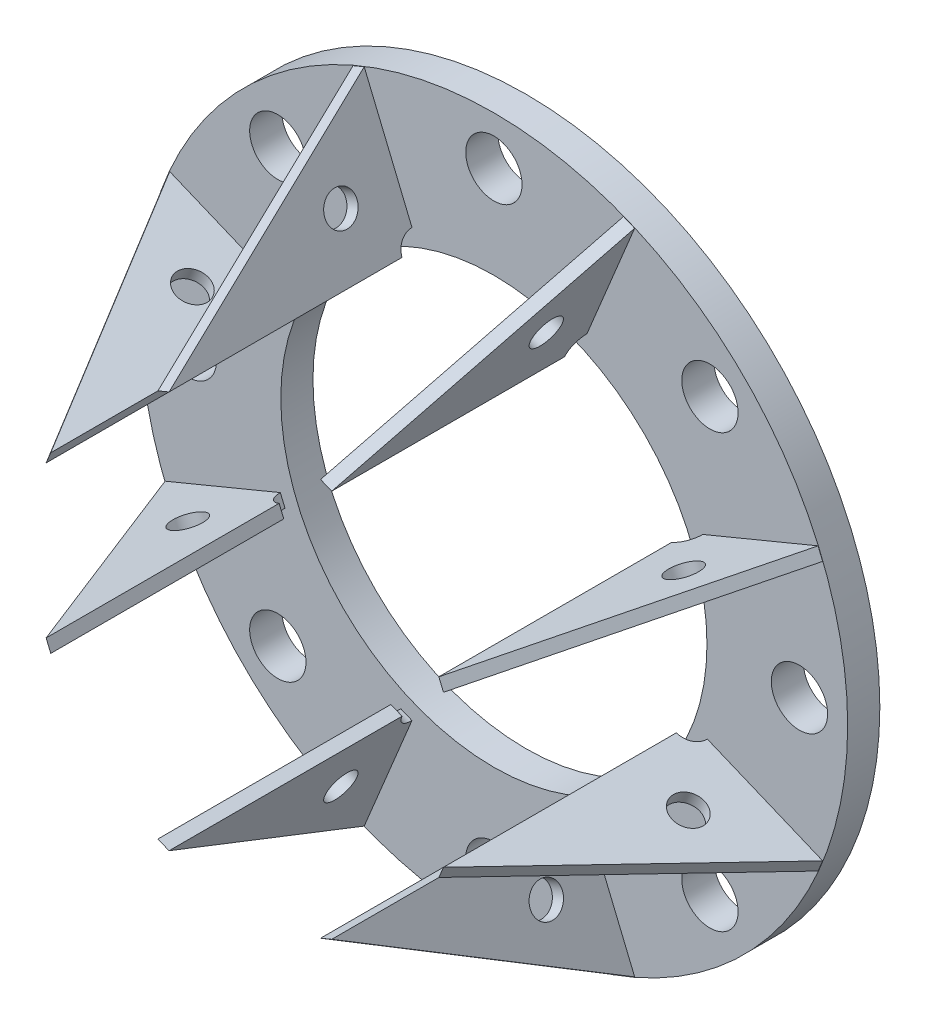
SolidWorks part; units mm, degrees
ref_plane "Front Plane" through (0, 0, 0) normal (0, 0, 1) x (1, 0, 0)
ref_plane "Top Plane" through (0, 0, 0) normal (0, 1, 0) x (1, 0, 0)
ref_plane "Right Plane" through (0, 0, 0) normal (1, 0, 0) x (0, 0, -1)
sketch "Sketch1" plane through (0, 0, 0) normal (0, 0, 1) x (1, 0, 0)
  circle A0 centre (0, 0) radius 84.1375
  circle A1 centre (0, 0) radius 139.7
  dimension "D1" = 168.275
  dimension "D2" = 279.4
extrude "Extrude1" add sketch "Sketch1" along normal blind 12.7
hole_wizard " (0.625) Diameter Hole1" positions "3DSketch1" profile "Sketch2" hole size "7/8" standard "Ansi Inch"
sketch3d "3DSketch1"
  line L10 (0, 139.7, 12.7) -> (0, 0, 12.7) construction
  circle A2 centre (0, 0, 12.7) radius 139.7 construction
  circle A3 centre (0, 0, 12.7) radius 139.7 construction
  point P5 (0, 120.65, 12.7)
  point P24 (0, 0, 152.4)
  point P26 (0, 0, 152.4)
  dimension "D1" = 120.65
sketch "Sketch2" plane through (0, 120.65, 12.7) normal (1, 0, 0) x (0, -1, 0)
  line L0 (0, 0) -> (0, 32.0771)
  line L1 (0, 32.0771) -> (11.1125, 25.4)
  line L2 (11.1125, 25.4) -> (11.1125, 0)
  line L5 (11.1125, 0) -> (0, 0)
  line L10 (0, 32.0771) -> (-11.1125, 25.4) construction
  line L11 (0, -6.35) -> (0, 107.95) construction
  dimension "Hole Dia." = 22.225
  dimension "Hole Depth" = 25.4
  dimension "Drill Angle" = 118
pattern_circular "CirPattern1" [suppressed] count 4 over 360 of bodies 102
pattern_circular "CirPattern2" count 8 over 360 about axis through (0, 0, 12.7) along (0, 0, -1) of " (0.625) Diameter Hole1"
sketch "Sketch4" plane through (0, 0, 12.7) normal (0, 0, 1) x (1, 0, 0)
  line L0 (0, 0) -> (0, 139.7) construction
  line L1 (0, 0) -> (-139.7, 0) construction
  line L2 (-99.3557, 98.2066) -> (-60.066, 58.9168) construction
  line L3 (-99.9167, 89.7873) -> (-68.4853, 58.3559)
  line L4 (-99.9167, 89.7873) -> (-90.9364, 98.7675)
  line L5 (-68.4853, 58.3559) -> (-59.5051, 67.3362)
  line L6 (-90.9364, 98.7675) -> (-59.5051, 67.3362)
  line L7 (-99.9167, 89.7873) -> (-59.5051, 67.3362) construction
  line L8 (-68.4853, 58.3559) -> (-90.9364, 98.7675) construction
  circle A0 centre (0, 0) radius 139.7 construction
  circle A1 centre (0, 0) radius 84.1375 construction
  point P12 (-79.7109, 78.5617)
  dimension "D1" = 45
  dimension "D2" = 12.7
extrude "Extrude2" [suppressed] add sketch "Sketch4" along normal blind 55.5625
sketch "Sketch5" [suppressed] plane through (-4.7316, -4.7316, 0) normal (-0.7071, -0.7071, 0) x (0, 0, 1)
  line L0 (57.15, 44.4487) -> (57.15, 88.8993)
  line L1 (57.15, 88.8993) -> (12.7, 88.8993)
  line L2 (12.7, 88.8993) -> (57.15, 44.4487)
extrude "Extrude3" [suppressed] cut sketch "Sketch5" against normal through all
pattern_circular "CirPattern3" [suppressed] count 4 over 360 of bodies 106
sketch "Sketch6" plane through (0, 0, 12.7) normal (0, 0, 1) x (1, 0, 0)
  line L0 (0, 0) -> (0, 139.7) construction
  line L1 (-55.5967, 127.9997) -> (-34.3132, 76.6169)
  line L2 (-53.4609, 129.066) -> (-32.049, 77.3732) construction
  line L3 (-55.5967, 127.9997) -> (-51.1967, 129.8223)
  line L4 (-34.3132, 76.6169) -> (-29.9132, 78.4394)
  line L5 (-51.1967, 129.8223) -> (-29.9132, 78.4394)
  line L6 (-55.5967, 127.9997) -> (-29.9132, 78.4394) construction
  line L7 (-34.3132, 76.6169) -> (-51.1967, 129.8223) construction
  line L8 (-32.049, 77.3732) -> (0, 0) construction
  circle A0 centre (0, 0) radius 139.7 construction
  point P9 (-42.755, 103.2196)
  dimension "D1" = 22.5
  dimension "D2" = 4.7625
extrude "Extrude4" add sketch "Sketch6" along normal blind 98.3456
sketch "Sketch8" plane through (2.2, 0.9113, 0) normal (0.9239, 0.3827, 0) x (0, 0, -1)
  line L0 (-12.7, 139.5323) -> (-111.0456, 83.9159)
  line L1 (-111.0456, 83.9159) -> (-111.0456, 139.5323)
  line L2 (-111.0456, 139.5323) -> (-12.7, 139.5323)
  line L3 (-12.7, 84.1038) -> (-12.7, 139.5323) construction
  line L4 (-111.0456, 83.9159) -> (-12.7, 83.9159) construction
  line L5 (-12.7, 90.2659) -> (-12.7, 83.9159)
  line L6 (-12.7, 83.9159) -> (-19.05, 83.9159)
  line L7 (-12.7, 83.9159) -> (-17.1901, 88.406) construction
  line L8 (-17.1901, 88.406) -> (-48.2258, 119.4417) construction
  circle A0 centre (-34.7554, 105.9713) radius 6.35
  arc A1 (-12.7, 90.2659) -> (-19.05, 83.9159) centre (-12.7, 83.9159) ccw
  dimension "D1" = 6.35
  dimension "D2" = 19.05
extrude "Extrude5" cut sketch "Sketch8" against normal up to next
pattern_circular "CirPattern4" count 8 over 360 about axis through (0, 0, 12.7) along (0, 0, -1) of "Extrude4", "Extrude5"
equation "\"D1@Extrude2\" = (\"D2@Sketch1\" - \"D1@Sketch1\")/2"
equation "\"D1@Extrude4\" = (\"D2@Sketch1\" - \"D1@Sketch1\") / 2 * 1.77"
